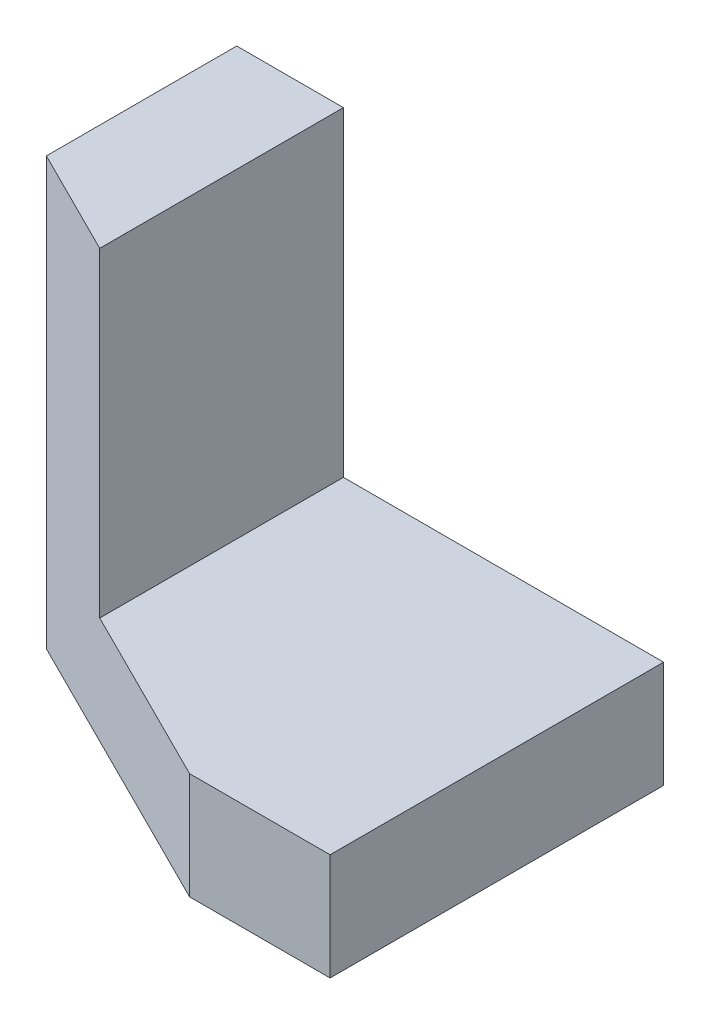
SolidWorks part; units mm, degrees
ref_plane "Front Plane" through (0, 0, 0) normal (0, 0, 1) x (1, 0, 0)
ref_plane "Top Plane" through (0, 0, 0) normal (0, 1, 0) x (1, 0, 0)
ref_plane "Right Plane" through (0, 0, 0) normal (1, 0, 0) x (0, 0, -1)
sketch "Sketch1" plane through (0, 0, 0) normal (0, 1, 0) x (1, 0, 0)
  line L0 (0, 0) -> (27.2621, -13.6311) construction
  line L2 (0, 0) -> (0, 18.1189)
  line L3 (0, 18.1189) -> (27.2621, 18.1189)
  line L5 (27.2621, -13.6311) -> (0, 0)
  line L6 (27.2621, -13.6311) -> (40.64, -13.6311)
  line L7 (27.2621, 18.1189) -> (40.64, 18.1189)
  line L8 (40.64, 18.1189) -> (40.64, -13.6311)
  dimension "D1" = 31.75
  dimension "D2" = 40.64
extrude "Boss-Extrude1" add sketch "Sketch1" along normal blind 10.16
sketch "Sketch2" plane through (0, 0, 0) normal (0, 1, 0) x (1, 0, 0)
  line L0 (0, 18.1189) -> (10.16, 18.1189)
  line L1 (40.64, 18.1189) -> (0, 18.1189) construction
  line L2 (10.16, 18.1189) -> (10.16, -5.08)
  line L3 (0, 0) -> (27.2621, -13.6311) construction
  line L4 (10.16, -5.08) -> (0, 0)
  line L5 (0, 0) -> (0, 18.1189)
  dimension "D1" = 10.16
extrude "Boss-Extrude2" add sketch "Sketch2" along normal blind 40.64
sketch "Sketch3" plane through (0, 0, 0) normal (1, 0, 0) x (0, 0, -1)
  line L0 (8.9608, 40.64) -> (0.6419, 13.7194)
  line L1 (-5.08, 40.64) -> (18.1189, 40.64) construction
  line L2 (31.3587, 113.1212) -> (0.6419, 13.7194) construction
  line L14 (-13.6311, 10.16) -> (18.1189, 10.16) construction
  line L15 (0.0635, 10.16) -> (0.1766, 11.684)
  line L16 (0.1766, 11.684) -> (0.6419, 13.7194)
  line L17 (8.9608, 40.64) -> (0, 40.64)
  line L21 (0.0635, 10.16) -> (0, 9.32)
  line L22 (0, 9.32) -> (0, 0)
  line L23 (0, 0) -> (-13.6311, 0)
  line L24 (-13.6311, 0) -> (-13.6311, 40.64)
  line L25 (-13.6311, 40.64) -> (8.9608, 40.64)
  ellipse E0 centre (17.5976, 4.9206) end of major axis (3.6855, 18.8328) minor radius 15.24 (0.6419, 13.7194) -> (0, 9.32) ccw construction
  dimension "D1" = 1.524
extrude "Cut-Extrude1" cut sketch "Sketch3" along normal through all rebuild error yes
